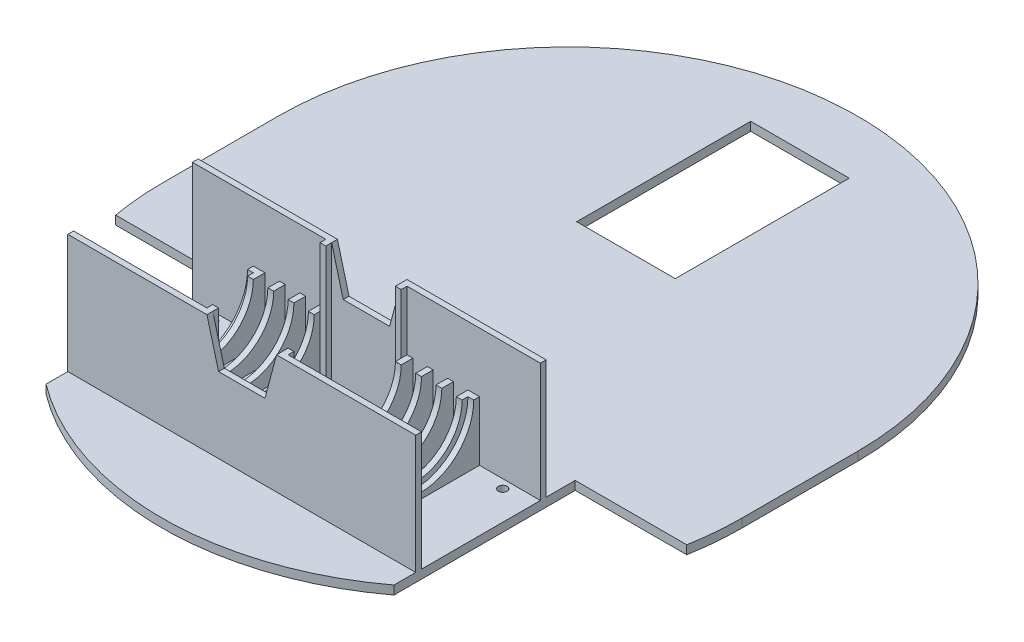
SolidWorks part; units mm, degrees
ref_plane "前视基准面" through (0, 0, 0) normal (0, 0, 1) x (1, 0, 0)
ref_plane "上视基准面" through (0, 0, 0) normal (0, 1, 0) x (1, 0, 0)
ref_plane "右视基准面" through (0, 0, 0) normal (1, 0, 0) x (0, 0, -1)
sketch "草图1" plane through (0, 0, 0) normal (0, 1, 0) x (1, 0, 0)
  line L1 (-100, 0) -> (100, 0)
  line L2 (-100, 0) -> (-100, 40)
  line L3 (-100, 40) -> (100, 40)
  line L4 (100, 0) -> (100, 40)
  circle A0 centre (0, 0) radius 100
  circle A1 centre (0, 40) radius 100
  dimension "D1" = 200
  dimension "D2" = 40
extrude "地盘基座" add sketch "草图1" along normal blind 3 contours A1 L1 A0 | L1 A1 A0 L3 | L3 A1 A0 | L3 A0 | L1 A1 | L3 A1 A0 | A1 A0 L1 | A0 A1 L3 | A1 L1 A0 | A1 A0 L4 | A1 L2 A0 region at (-96.9033, 0, -6.6371) region at (0, 0, 60.4644) region at (-99.3949, 0, -20) region at (0, 0, -20) region at (0, 0, 24.749) region at (0, 0, -100.4644) region at (-96.9033, 0, -33.3629) region at (99.3949, 0, -20) region at (96.9033, 0, -6.6371) region at (0, 0, -64.749) region at (96.9033, 0, -33.3629)
sketch "草图2" plane through (0, 3, 0) normal (0, 1, 0) x (1, 0, 0)
  line L0 (0, -34.3678) -> (0, -61.7856)
  line L1 (60, -17.5) -> (60, -82.5)
  line L2 (-100, -17.5) -> (-60, -17.5)
  line L3 (-100, -17.5) -> (-100, -82.5)
  line L4 (-100, -82.5) -> (-60, -82.5)
  line L5 (-60, -17.5) -> (-60, -82.5)
  line L6 (100, -82.5) -> (60, -82.5)
  line L7 (100, -17.5) -> (100, -82.5)
  line L8 (100, -17.5) -> (60, -17.5)
  point P7 (-60, -50)
  arc M8 (-100, 0) -> (100, 0) centre (0, 0) ccw
  dimension "D1" = 60
  dimension "D2" = 50
  dimension "D3" = 40
  dimension "D4" = 65
extrude "后轮开口" cut sketch "草图2" against normal blind 3 contours L5 L2 M8 | L8 L1 M8 region at (74.7743, 3, 40.9759) region at (-74.7743, 3, 40.9759)
sketch "草图3" plane through (0, 3, 0) normal (0, 1, 0) x (1, 0, 0)
  line L1 (-17, 120) -> (17, 120)
  line L2 (-17, 120) -> (-17, 60)
  line L3 (-17, 60) -> (17, 60)
  line L4 (17, 120) -> (17, 60)
  line L5 (-17, 120) -> (17, 60) construction
  line L6 (-17, 60) -> (17, 120) construction
  point P0 (0, 90)
  dimension "D1" = 90
  dimension "D2" = 60
  dimension "D3" = 34
extrude "前轮开口" cut sketch "草图3" against normal blind 3
sketch "草图4" plane through (0, 3, 0) normal (0, 1, 0) x (1, 0, 0)
  line L0 (-24.4844, -50) -> (31.2042, -50)
  line L1 (-60, -17.5) -> (-60, -80) construction
  line L2 (-60, -27.5) -> (60, -27.5)
  line L3 (-60, -27.5) -> (-60, -29.5)
  line L4 (-60, -29.5) -> (60, -29.5)
  line L5 (60, -27.5) -> (60, -29.5)
  line L6 (60, -17.5) -> (60, -80) construction
  line L7 (60, -72.5) -> (60, -70.5)
  line L8 (-60, -70.5) -> (60, -70.5)
  line L9 (-60, -72.5) -> (-60, -70.5)
  line L10 (-60, -72.5) -> (60, -72.5)
  line M8 (60, -80) -> (60, -17.5)
  line M16 (-60, -17.5) -> (-60, -80)
  dimension "D1" = 50
  dimension "D2" = 2
  dimension "D3" = 20.5
extrude "电机横向承重结构" add sketch "草图4" along normal blind 41 contours L10 L8 M16 M8 | L4 L5 L2 L3 region at (0, 3, 71.5)
sketch "草图5" plane through (0, 3, 0) normal (0, 1, 0) x (1, 0, 0)
  line L0 (0, -39.9794) -> (0, -58.7668)
  line L1 (-60, -29.5) -> (60, -29.5) construction
  line L2 (-35, -29.5) -> (-39, -29.5)
  line L3 (-35, -29.5) -> (-35, -70.5)
  line L4 (-35, -70.5) -> (-39, -70.5)
  line L5 (-39, -29.5) -> (-39, -70.5)
  line L6 (-60, -70.5) -> (60, -70.5) construction
  line L8 (-60, -29.5) -> (-60, -70.5) construction
  line L9 (39, -29.5) -> (39, -70.5)
  line L10 (35, -70.5) -> (39, -70.5)
  line L11 (35, -29.5) -> (35, -70.5)
  line L12 (35, -29.5) -> (39, -29.5)
  line L13 (-60, -29.5) -> (60, -29.5) construction
  line L14 (-30, -29.5) -> (-28, -29.5)
  line L15 (-30, -29.5) -> (-30, -70.5)
  line L16 (-30, -70.5) -> (-28, -70.5)
  line L17 (-28, -29.5) -> (-28, -70.5)
  line L18 (-60, -70.5) -> (60, -70.5) construction
  line L19 (-23, -29.5) -> (-21, -29.5)
  line L20 (-23, -29.5) -> (-23, -70.5)
  line L21 (-23, -70.5) -> (-21, -70.5)
  line L22 (-21, -29.5) -> (-21, -70.5)
  line L23 (-16, -29.5) -> (-14, -29.5)
  line L24 (-16, -29.5) -> (-16, -70.5)
  line L25 (-16, -70.5) -> (-14, -70.5)
  line L26 (-14, -29.5) -> (-14, -70.5)
  line L27 (30, -29.5) -> (28, -29.5)
  line L28 (30, -29.5) -> (30, -70.5)
  line L29 (30, -70.5) -> (28, -70.5)
  line L30 (28, -29.5) -> (28, -70.5)
  line L32 (23, -70.5) -> (21, -70.5)
  line L33 (23, -70.5) -> (23, -29.5)
  line L34 (23, -29.5) -> (21, -29.5)
  line L35 (21, -70.5) -> (21, -29.5)
  line L36 (16, -29.5) -> (14, -29.5)
  line L37 (16, -29.5) -> (16, -70.5)
  line L38 (16, -70.5) -> (14, -70.5)
  line L39 (14, -29.5) -> (14, -70.5)
  line M6 (60, -29.5) -> (-60, -29.5)
  line M8 (-60, -70.5) -> (60, -70.5)
  dimension "D1" = 21
  dimension "D2" = 4
  dimension "D3" = 2
  dimension "D4" = 2
  dimension "D5" = 2
  dimension "D6" = 2
  dimension "D7" = 2
  dimension "D8" = 2
  dimension "D9" = 5
  dimension "D10" = 5
  dimension "D11" = 5
  dimension "D12" = 5
  dimension "D13" = 5
  dimension "D14" = 5
extrude "电机纵向承重结构" add sketch "草图5" along normal blind 20.5 contours L5 L3 M6 M8 | L11 L9 M6 M8 | L22 L20 M6 M8 | L26 L24 M6 M8 | L35 L33 M8 M6 | L30 L28 M6 M8 | L17 L16 L15 L14 | L37 L38 L39 L36 region at (-37, 3, 50) region at (-22, 3, 50) region at (-15, 3, 50) region at (22, 3, 50) region at (29, 3, 50) region at (37, 3, 50)
sketch "草图10" plane through (0, 3, 0) normal (0, 1, 0) x (1, 0, 0)
  line L0 (-60, -29.5) -> (-60, -70.5) construction
  line L1 (-60, -70.5) -> (60, -70.5) construction
  line L2 (-60, -29.5) -> (60, -29.5) construction
  line L3 (0, -37.264) -> (0, -56.5171)
  circle A0 centre (-50, -32.5) radius 1.5
  circle A1 centre (-50, -67.5) radius 1.5
  circle A2 centre (50, -67.5) radius 1.5
  circle A3 centre (50, -32.5) radius 1.5
  dimension "D1" = 3
  dimension "D4" = 3
  dimension "D5" = 3
  dimension "D2" = 10
  dimension "D3" = 3
  dimension "D6" = 10
extrude "电机螺丝孔（下）" cut sketch "草图10" against normal through all contours A0 | A1 | A3 | A2 region at (-50, 3, 32.5) region at (-50, 3, 67.5) region at (50, 3, 67.5) region at (50, 3, 32.5)
sketch "草图6" plane through (-39, 0, 0) normal (-1, 0, 0) x (0, 0, 1)
  line L1 (29.5, 23.5) -> (70.5, 23.5) construction
  circle A0 centre (50, 23.5) radius 18.5
  line M3 (70.5, 23.5) -> (29.5, 23.5)
  dimension "D1" = 37
extrude "左电机卡槽大" cut sketch "草图6" against normal blind 2 contours A0 M3 region at (-39, 15.6484, 50)
sketch "草图8" plane through (39, 0, 0) normal (1, 0, 0) x (0, 0, -1)
  line L1 (-29.5, 23.5) -> (-70.5, 23.5) construction
  circle A0 centre (-50, 23.5) radius 18.5
  line M3 (-29.5, 23.5) -> (-70.5, 23.5)
  dimension "D1" = 37
extrude "右电机卡槽大" cut sketch "草图8" against normal blind 2 contours A0 M3 region at (39, 15.6484, 50)
sketch "草图11" plane through (-37, 0, 0) normal (-1, 0, 0) x (0, 0, 1)
  line L0 (68.5, 23.5) -> (31.5, 23.5) construction
  circle A0 centre (50, 23.5) radius 16.5
  dimension "D1" = 33
extrude "左电机卡槽小" cut sketch "草图11" against normal blind 23
sketch "草图12" plane through (37, 0, 0) normal (1, 0, 0) x (0, 0, -1)
  line L0 (-31.5, 23.5) -> (-68.5, 23.5) construction
  circle A0 centre (-50, 23.5) radius 16.5
  dimension "D1" = 33
extrude "右电机卡槽小" cut sketch "草图12" against normal blind 23
sketch "草图13" plane through (0, 0, 72.5) normal (0, 0, 1) x (1, 0, 0)
  line L0 (-8, 29) -> (8, 29)
  line L1 (8, 29) -> (12, 44)
  line L2 (-60, 44) -> (60, 44) construction
  line L3 (12, 44) -> (-12, 44)
  line L4 (-12, 44) -> (-8, 29)
  point P2 (0, 29)
  point P7 (0, 44)
  dimension "D1" = 0
  dimension "D2" = 0
  dimension "D3" = 16
  dimension "D4" = 24
  dimension "D5" = 15
extrude "电机线开口" cut sketch "草图13" against normal blind 45
sketch "草图14" plane through (0, 3, 0) normal (0, 1, 0) x (1, 0, 0)
  line L0 (-14, -66.5) -> (-14, -70.5) construction
  line L1 (-14, -29.5) -> (-12, -29.5)
  line L2 (-14, -29.5) -> (-14, -31.5)
  line L3 (-14, -31.5) -> (-12, -31.5)
  line L4 (-12, -29.5) -> (-12, -31.5)
  line L5 (-14, -70.5) -> (-12, -70.5)
  line L6 (-14, -70.5) -> (-14, -68.5)
  line L7 (-14, -68.5) -> (-12, -68.5)
  line L8 (-12, -70.5) -> (-12, -68.5)
  line L9 (-60, -70.5) -> (-12, -70.5) construction
  line L11 (14, -70.5) -> (12, -70.5)
  line L12 (14, -70.5) -> (14, -68.5)
  line L13 (14, -68.5) -> (12, -68.5)
  line L14 (12, -70.5) -> (12, -68.5)
  line L15 (14, -29.5) -> (12, -29.5)
  line L16 (14, -29.5) -> (14, -31.5)
  line L17 (14, -31.5) -> (12, -31.5)
  line L18 (12, -29.5) -> (12, -31.5)
  line M8 (-14, -70.5) -> (14, -70.5)
  line M9 (14, -70.5) -> (14, -29.5)
  line M10 (14, -29.5) -> (-14, -29.5)
  line M11 (-14, -29.5) -> (-14, -70.5)
  dimension "D1" = 2
  dimension "D2" = 2
  dimension "D3" = 2
  dimension "D4" = 2
  dimension "D5" = 2
  dimension "D6" = 2
  dimension "D7" = 2
  dimension "D8" = 2
extrude "锁架锁槽" add sketch "草图14" along normal blind 41 contours L4 L3 M10 M11 | L18 L17 M10 M9 | L14 L13 M8 M9 | L8 L7 M8 M11 region at (-13, 3, 30.5) region at (13, 3, 30.5) region at (-13, 3, 69.5) region at (13, 3, 69.5)
